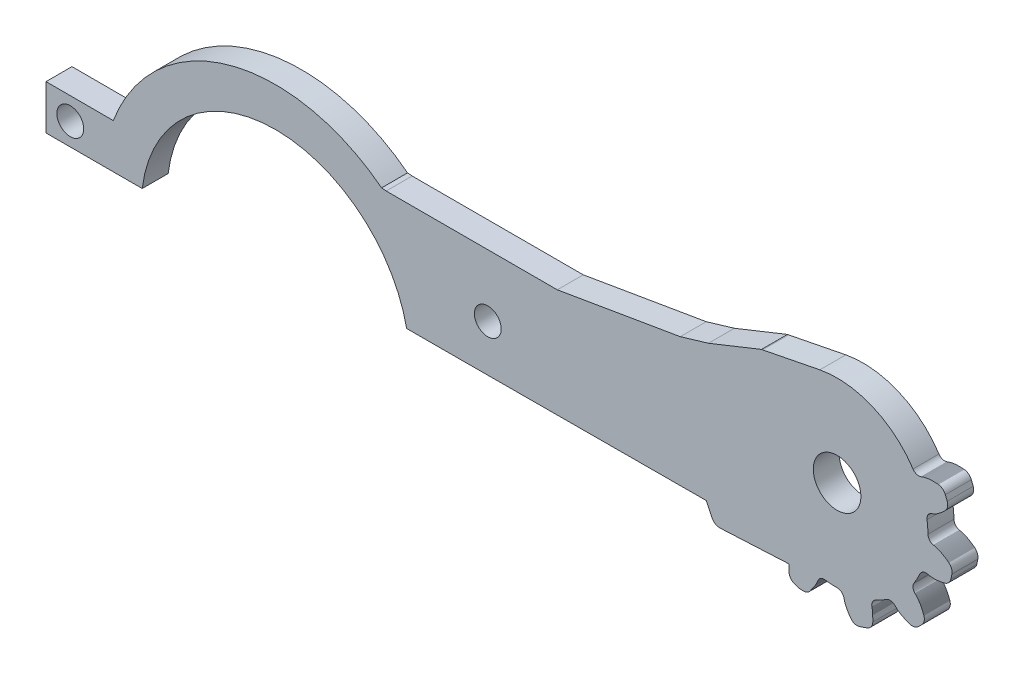
SolidWorks part; units mm, degrees
ref_plane "前视基准面" through (0, 0, 0) normal (0, 0, 1) x (1, 0, 0)
ref_plane "上视基准面" through (0, 0, 0) normal (0, 1, 0) x (1, 0, 0)
ref_plane "右视基准面" through (0, 0, 0) normal (1, 0, 0) x (0, 0, -1)
sketch "Model" plane through (0, 0, 0) normal (0, 0, 1) x (1, 0, 0)
  line L0 (3139.6381, 1742.7841) -> (3139.6125, 1742.8095)
  line L1 (3139.6635, 1742.7586) -> (3139.6381, 1742.7841)
  line L2 (3139.8365, 1742.5753) -> (3139.8124, 1742.602)
  line L3 (3153.0408, 1740.3213) -> (3153.0525, 1740.3554)
  line L4 (3153.0289, 1740.2873) -> (3153.0408, 1740.3213)
  line L5 (3153.0169, 1740.2533) -> (3153.0289, 1740.2873)
  line L6 (3153.0046, 1740.2194) -> (3153.0169, 1740.2533)
  line L7 (3152.9921, 1740.1856) -> (3153.0046, 1740.2194)
  line L8 (3152.9795, 1740.1519) -> (3152.9921, 1740.1856)
  line L9 (3152.87, 1739.8856) -> (3152.8846, 1739.9185)
  line L10 (3152.8242, 1739.788) -> (3152.8398, 1739.8203)
  line L11 (3154.7478, 1736.7119) -> (3154.7132, 1736.7018)
  line L12 (3154.7825, 1736.7216) -> (3154.7478, 1736.7119)
  line L13 (3154.8172, 1736.7308) -> (3154.7825, 1736.7216)
  line L14 (3154.8521, 1736.7395) -> (3154.8172, 1736.7308)
  line L15 (3154.8871, 1736.7479) -> (3154.8521, 1736.7395)
  line L16 (3154.9222, 1736.7557) -> (3154.8871, 1736.7479)
  line L17 (3154.9574, 1736.7631) -> (3154.9222, 1736.7557)
  line L18 (3154.9926, 1736.77) -> (3154.9574, 1736.7631)
  line L19 (3155.028, 1736.7765) -> (3154.9926, 1736.77)
  line L20 (3155.0634, 1736.7826) -> (3155.028, 1736.7765)
  line L21 (3155.1344, 1736.7936) -> (3155.0989, 1736.7883)
  line L22 (3155.17, 1736.7985) -> (3155.1344, 1736.7936)
  line L23 (3156.468, 1733.9968) -> (3156.497, 1734.0182)
  line L24 (3156.4389, 1733.9757) -> (3156.468, 1733.9968)
  line L25 (3156.4096, 1733.9547) -> (3156.4389, 1733.9757)
  line L26 (3156.3802, 1733.9339) -> (3156.4096, 1733.9547)
  line L27 (3156.3506, 1733.9134) -> (3156.3802, 1733.9339)
  line L28 (3156.3209, 1733.8931) -> (3156.3506, 1733.9134)
  line L29 (3156.291, 1733.8731) -> (3156.3209, 1733.8931)
  line L30 (3156.2609, 1733.8533) -> (3156.291, 1733.8731)
  line L31 (3156.2307, 1733.8339) -> (3156.2609, 1733.8533)
  line L32 (3156.2003, 1733.8148) -> (3156.2307, 1733.8339)
  line L33 (3156.1696, 1733.796) -> (3156.2003, 1733.8148)
  line L34 (3156.4614, 1730.0427) -> (3156.4285, 1730.0571)
  line L35 (3156.4942, 1730.028) -> (3156.4614, 1730.0427)
  line L36 (3156.5269, 1730.0129) -> (3156.4942, 1730.028)
  line L37 (3155.2801, 1726.9965) -> (3155.3155, 1726.99)
  line L38 (3155.2448, 1727.0034) -> (3155.2801, 1726.9965)
  line L39 (3155.1394, 1727.0265) -> (3155.1744, 1727.0185)
  line L40 (3155.1044, 1727.035) -> (3155.1394, 1727.0265)
  line L41 (3154.7261, 1727.0734) -> (3155.1044, 1727.035)
  line L42 (3139.9527, 1742.4382) -> (3139.9301, 1742.4661)
  line L43 (3139.9751, 1742.4101) -> (3139.9527, 1742.4382)
  line L44 (3152.9666, 1740.1183) -> (3152.9795, 1740.1519)
  line L45 (3152.9267, 1740.0179) -> (3152.9402, 1740.0512)
  line L46 (3152.8989, 1739.9515) -> (3152.9129, 1739.9846)
  line L47 (3152.8846, 1739.9185) -> (3152.8989, 1739.9515)
  line L48 (3155.3488, 1736.8185) -> (3155.313, 1736.8151)
  line L49 (3152.8551, 1739.8529) -> (3152.87, 1739.8856)
  line L50 (3152.8398, 1739.8203) -> (3152.8551, 1739.8529)
  line L51 (3152.8082, 1739.7558) -> (3152.8242, 1739.788)
  line L52 (3152.7919, 1739.7238) -> (3152.8082, 1739.7558)
  line L53 (3155.2095, 1727.0108) -> (3155.2448, 1727.0034)
  line L54 (3155.951, 1730.2151) -> (3155.916, 1730.2232)
  line L55 (3139.8603, 1742.5483) -> (3139.8365, 1742.5753)
  line L56 (3139.8838, 1742.5212) -> (3139.8603, 1742.5483)
  line L57 (3139.9071, 1742.4938) -> (3139.8838, 1742.5212)
  line L58 (3139.9301, 1742.4661) -> (3139.9071, 1742.4938)
  line L59 (3139.997, 1742.3817) -> (3139.9751, 1742.4101)
  line L60 (3152.9535, 1740.0847) -> (3152.9666, 1740.1183)
  line L61 (3152.9402, 1740.0512) -> (3152.9535, 1740.0847)
  line L62 (3140.0607, 1742.2947) -> (3140.0399, 1742.324)
  line L63 (3155.2057, 1736.8031) -> (3155.17, 1736.7985)
  line L64 (3152.9129, 1739.9846) -> (3152.9267, 1740.0179)
  line L65 (3156.497, 1734.0182) -> (3156.5259, 1734.0397)
  line L66 (3154.179, 1723.2587) -> (3154.162, 1723.2905)
  line L67 (3154.1959, 1723.2269) -> (3154.179, 1723.2587)
  line L68 (3154.2125, 1723.1949) -> (3154.1959, 1723.2269)
  line L69 (3154.2289, 1723.1628) -> (3154.2125, 1723.1949)
  line L70 (3154.2452, 1723.1307) -> (3154.2289, 1723.1628)
  line L71 (3154.2612, 1723.0984) -> (3154.2452, 1723.1307)
  line L72 (3154.277, 1723.066) -> (3154.2612, 1723.0984)
  line L73 (3154.2927, 1723.0336) -> (3154.277, 1723.066)
  line L74 (3154.3081, 1723.001) -> (3154.2927, 1723.0336)
  line L75 (3154.3338, 1722.9732) -> (3154.3081, 1723.001)
  line L76 (3152.3422, 1721.044) -> (3152.3796, 1721.0389)
  line L77 (3152.3097, 1721.0596) -> (3152.3422, 1721.044)
  line L78 (3152.2773, 1721.0754) -> (3152.3097, 1721.0596)
  line L79 (3155.0989, 1736.7883) -> (3155.0634, 1736.7826)
  line L80 (3140.0399, 1742.324) -> (3140.0186, 1742.353)
  line L81 (3156.0903, 1730.1784) -> (3156.0556, 1730.1882)
  line L82 (3156.1248, 1730.1682) -> (3156.0903, 1730.1784)
  line L83 (3152.2451, 1721.0914) -> (3152.2773, 1721.0754)
  line L84 (3152.2129, 1721.1075) -> (3152.2451, 1721.0914)
  line L85 (3156.4285, 1730.0571) -> (3156.3954, 1730.0711)
  line L86 (3146.7836, 1742.877) -> (3146.781, 1742.9128)
  line L87 (3146.7858, 1742.8411) -> (3146.7836, 1742.877)
  line L88 (3146.7875, 1742.8052) -> (3146.7858, 1742.8411)
  line L89 (3146.7888, 1742.7692) -> (3146.7875, 1742.8052)
  line L90 (3146.7896, 1742.7333) -> (3146.7888, 1742.7692)
  line L91 (3146.7899, 1742.6973) -> (3146.7896, 1742.7333)
  line L92 (3146.7898, 1742.6613) -> (3146.7899, 1742.6973)
  line L93 (3146.7893, 1742.6253) -> (3146.7898, 1742.6613)
  line L94 (3146.7883, 1742.5893) -> (3146.7893, 1742.6253)
  line L95 (3146.7869, 1742.5533) -> (3146.7883, 1742.5893)
  line L96 (3146.7851, 1742.5174) -> (3146.7869, 1742.5533)
  line L97 (3146.7828, 1742.4815) -> (3146.7851, 1742.5174)
  line L98 (3146.7802, 1742.4456) -> (3146.7828, 1742.4815)
  line L99 (3146.7772, 1742.4097) -> (3146.7802, 1742.4456)
  line L100 (3146.7738, 1742.374) -> (3146.7772, 1742.4097)
  line L101 (3146.7513, 1741.9979) -> (3146.7738, 1742.374)
  line L102 (3149.8509, 1741.2183) -> (3149.6326, 1740.9116)
  line L103 (3140.0186, 1742.353) -> (3139.997, 1742.3817)
  line L104 (3149.8719, 1741.2475) -> (3149.8509, 1741.2183)
  line L105 (3149.8932, 1741.2765) -> (3149.8719, 1741.2475)
  line L106 (3149.9149, 1741.3052) -> (3149.8932, 1741.2765)
  line L107 (3155.2414, 1736.8074) -> (3155.2057, 1736.8031)
  line L108 (3155.2772, 1736.8114) -> (3155.2414, 1736.8074)
  line L109 (3155.313, 1736.8151) -> (3155.2772, 1736.8114)
  line L110 (3156.4629, 1726.9866) -> (3156.4986, 1726.9911)
  line L111 (3156.4271, 1726.9824) -> (3156.4629, 1726.9866)
  line L112 (3155.986, 1730.2065) -> (3155.951, 1730.2151)
  line L113 (3156.0209, 1730.1976) -> (3155.986, 1730.2065)
  line L114 (3156.0556, 1730.1882) -> (3156.0209, 1730.1976)
  line L115 (3156.1592, 1730.1576) -> (3156.1248, 1730.1682)
  line L116 (3156.7523, 1734.2181) -> (3156.7799, 1734.2412)
  line L117 (3156.7245, 1734.1952) -> (3156.7523, 1734.2181)
  line L118 (3156.6965, 1734.1725) -> (3156.7245, 1734.1952)
  line L119 (3156.6684, 1734.1499) -> (3156.6965, 1734.1725)
  line L120 (3156.6402, 1734.1275) -> (3156.6684, 1734.1499)
  line L121 (3156.6118, 1734.1053) -> (3156.6402, 1734.1275)
  line L122 (3156.5833, 1734.0833) -> (3156.6118, 1734.1053)
  line L123 (3156.5547, 1734.0614) -> (3156.5833, 1734.0833)
  line L124 (3156.5259, 1734.0397) -> (3156.5547, 1734.0614)
  line L125 (3153.0639, 1740.3896) -> (3153.0751, 1740.4238)
  line L126 (3153.0525, 1740.3554) -> (3153.0639, 1740.3896)
  line L127 (3155.2459, 1733.3476) -> (3155.5833, 1733.5244)
  line L128 (3156.1934, 1730.1466) -> (3156.1592, 1730.1576)
  line L129 (3156.2275, 1730.1351) -> (3156.1934, 1730.1466)
  line L130 (3156.2615, 1730.1232) -> (3156.2275, 1730.1351)
  line L131 (3156.2952, 1730.1108) -> (3156.2615, 1730.1232)
  line L132 (3156.3288, 1730.098) -> (3156.2952, 1730.1108)
  line L133 (3156.3622, 1730.0848) -> (3156.3288, 1730.098)
  line L134 (3156.3954, 1730.0711) -> (3156.3622, 1730.0848)
  line L135 (3143.5454, 1743.0444) -> (3143.5389, 1743.0091)
  line L136 (3143.5524, 1743.0797) -> (3143.5454, 1743.0444)
  line L137 (3143.5598, 1743.1149) -> (3143.5524, 1743.0797)
  line L138 (3143.5677, 1743.15) -> (3143.5598, 1743.1149)
  line L139 (3143.5761, 1743.1849) -> (3143.5677, 1743.15)
  line L140 (3143.5848, 1743.2197) -> (3143.5761, 1743.1849)
  line L141 (3143.594, 1743.2545) -> (3143.5848, 1743.2197)
  line L142 (3143.6036, 1743.2891) -> (3143.594, 1743.2545)
  line L143 (3143.6135, 1743.3237) -> (3143.6036, 1743.2891)
  line L144 (3143.6345, 1743.3925) -> (3143.6238, 1743.3581)
  line L145 (3143.6454, 1743.4267) -> (3143.6345, 1743.3925)
  line L146 (3143.6567, 1743.4609) -> (3143.6454, 1743.4267)
  line L147 (3143.6682, 1743.495) -> (3143.6567, 1743.4609)
  line L148 (3143.68, 1743.5291) -> (3143.6682, 1743.495)
  line L149 (3143.686, 1743.546) -> (3143.68, 1743.5291)
  line L150 (3156.1388, 1733.7775) -> (3156.1696, 1733.796)
  line L151 (3156.1077, 1733.7594) -> (3156.1388, 1733.7775)
  line L152 (3155.5833, 1733.5244) -> (3155.6173, 1733.5362)
  line L153 (3155.8104, 1730.2453) -> (3155.4407, 1730.3164)
  line L154 (3155.8457, 1730.2383) -> (3155.8104, 1730.2453)
  line L155 (3155.8809, 1730.231) -> (3155.8457, 1730.2383)
  line L156 (3155.916, 1730.2232) -> (3155.8809, 1730.231)
  line L157 (3146.7256, 1743.3043) -> (3146.7187, 1743.3396)
  line L158 (3146.7323, 1743.2689) -> (3146.7256, 1743.3043)
  line L159 (3146.7387, 1743.2335) -> (3146.7323, 1743.2689)
  line L160 (3146.7448, 1743.198) -> (3146.7387, 1743.2335)
  line L161 (3146.7506, 1743.1625) -> (3146.7448, 1743.198)
  line L162 (3146.7561, 1743.127) -> (3146.7506, 1743.1625)
  line L163 (3146.7612, 1743.0914) -> (3146.7561, 1743.127)
  line L164 (3146.7659, 1743.0557) -> (3146.7612, 1743.0914)
  line L165 (3146.7703, 1743.0201) -> (3146.7659, 1743.0557)
  line L166 (3146.7743, 1742.9844) -> (3146.7703, 1743.0201)
  line L167 (3146.7779, 1742.9486) -> (3146.7743, 1742.9844)
  line L168 (3146.781, 1742.9128) -> (3146.7779, 1742.9486)
  line L169 (3153.0969, 1740.4925) -> (3153.0997, 1740.5293)
  line L170 (3156.0765, 1733.7417) -> (3156.1077, 1733.7594)
  line L171 (3155.7852, 1733.6007) -> (3155.8184, 1733.6147)
  line L172 (3155.7519, 1733.587) -> (3155.7852, 1733.6007)
  line L173 (3155.7185, 1733.5737) -> (3155.7519, 1733.587)
  line L174 (3155.6849, 1733.5608) -> (3155.7185, 1733.5737)
  line L175 (3155.6512, 1733.5483) -> (3155.6849, 1733.5608)
  line L176 (3155.6173, 1733.5362) -> (3155.6512, 1733.5483)
  line L177 (3151.8657, 1721.2984) -> (3151.8967, 1721.28)
  line L178 (3152.7752, 1739.692) -> (3152.7919, 1739.7238)
  line L179 (3152.7225, 1739.5979) -> (3152.7405, 1739.629)
  line L180 (3139.5087, 1742.9095) -> (3139.4824, 1742.9341)
  line L181 (3139.5349, 1742.8847) -> (3139.5087, 1742.9095)
  line L182 (3139.5609, 1742.8598) -> (3139.5349, 1742.8847)
  line L183 (3139.5868, 1742.8347) -> (3139.5609, 1742.8598)
  line L184 (3139.6125, 1742.8095) -> (3139.5868, 1742.8347)
  line L185 (3154.5424, 1736.6452) -> (3154.5087, 1736.6328)
  line L186 (3139.6888, 1742.7329) -> (3139.6635, 1742.7586)
  line L187 (3139.7139, 1742.707) -> (3139.6888, 1742.7329)
  line L188 (3139.7388, 1742.6811) -> (3139.7139, 1742.707)
  line L189 (3139.7635, 1742.6549) -> (3139.7388, 1742.6811)
  line L190 (3139.7881, 1742.6285) -> (3139.7635, 1742.6549)
  line L191 (3139.8124, 1742.602) -> (3139.7881, 1742.6285)
  line L192 (3140.0812, 1742.2651) -> (3140.0607, 1742.2947)
  line L193 (3140.1013, 1742.2353) -> (3140.0812, 1742.2651)
  line L194 (3140.1211, 1742.2052) -> (3140.1013, 1742.2353)
  line L195 (3140.1404, 1742.1748) -> (3140.1211, 1742.2052)
  line L196 (3140.1594, 1742.1443) -> (3140.1404, 1742.1748)
  line L197 (3140.1781, 1742.1135) -> (3140.1594, 1742.1443)
  line L198 (3140.1963, 1742.0824) -> (3140.1781, 1742.1135)
  line L199 (3140.2143, 1742.0512) -> (3140.1963, 1742.0824)
  line L200 (3140.2318, 1742.0198) -> (3140.2143, 1742.0512)
  line L201 (3140.249, 1741.9882) -> (3140.2318, 1742.0198)
  line L202 (3140.2658, 1741.9564) -> (3140.249, 1741.9882)
  line L203 (3140.2823, 1741.9245) -> (3140.2658, 1741.9564)
  line L204 (3140.4359, 1741.5802) -> (3140.2823, 1741.9245)
  line L205 (3143.4957, 1742.6159) -> (3143.4779, 1742.2399)
  line L206 (3143.4976, 1742.6518) -> (3143.4957, 1742.6159)
  line L207 (3143.4999, 1742.6877) -> (3143.4976, 1742.6518)
  line L208 (3143.5026, 1742.7235) -> (3143.4999, 1742.6877)
  line L209 (3143.5056, 1742.7594) -> (3143.5026, 1742.7235)
  line L210 (3143.5091, 1742.7952) -> (3143.5056, 1742.7594)
  line L211 (3143.513, 1742.831) -> (3143.5091, 1742.7952)
  line L212 (3143.5173, 1742.8668) -> (3143.513, 1742.831)
  line L213 (3143.5221, 1742.9024) -> (3143.5173, 1742.8668)
  line L214 (3143.5272, 1742.9381) -> (3143.5221, 1742.9024)
  line L215 (3143.5329, 1742.9736) -> (3143.5272, 1742.9381)
  line L216 (3143.5389, 1743.0091) -> (3143.5329, 1742.9736)
  line L217 (3154.0741, 1723.4476) -> (3154.0559, 1723.4787)
  line L218 (3154.0921, 1723.4164) -> (3154.0741, 1723.4476)
  line L219 (3154.1099, 1723.3851) -> (3154.0921, 1723.4164)
  line L220 (3154.1274, 1723.3537) -> (3154.1099, 1723.3851)
  line L221 (3154.1448, 1723.3221) -> (3154.1274, 1723.3537)
  line L222 (3154.162, 1723.2905) -> (3154.1448, 1723.3221)
  line L223 (3150.8201, 1742.1198) -> (3150.7904, 1742.0996)
  line L224 (3150.85, 1742.1399) -> (3150.8201, 1742.1198)
  line L225 (3150.8801, 1742.1598) -> (3150.85, 1742.1399)
  line L226 (3150.9061, 1742.1859) -> (3150.8801, 1742.1598)
  line L227 (3153.0861, 1740.4581) -> (3153.0969, 1740.4925)
  line L228 (3153.0751, 1740.4238) -> (3153.0861, 1740.4581)
  line L229 (3156.045, 1733.7244) -> (3156.0765, 1733.7417)
  line L230 (3156.0133, 1733.7075) -> (3156.045, 1733.7244)
  line L231 (3155.9491, 1733.675) -> (3155.9813, 1733.691)
  line L232 (3155.9167, 1733.6593) -> (3155.9491, 1733.675)
  line L233 (3155.8841, 1733.644) -> (3155.9167, 1733.6593)
  line L234 (3155.8513, 1733.6292) -> (3155.8841, 1733.644)
  line L235 (3155.8184, 1733.6147) -> (3155.8513, 1733.6292)
  line L236 (3152.0851, 1721.1742) -> (3152.1169, 1721.1573)
  line L237 (3152.0534, 1721.1914) -> (3152.0851, 1721.1742)
  line L238 (3152.0218, 1721.2087) -> (3152.0534, 1721.1914)
  line L239 (3151.9904, 1721.2263) -> (3152.0218, 1721.2087)
  line L240 (3151.959, 1721.244) -> (3151.9904, 1721.2263)
  line L241 (3151.9278, 1721.2619) -> (3151.959, 1721.244)
  line L242 (3151.8967, 1721.28) -> (3151.9278, 1721.2619)
  line L243 (3150.0998, 1741.5257) -> (3150.0755, 1741.4992)
  line L244 (3151.7135, 1721.3942) -> (3151.7436, 1721.3744)
  line L245 (3151.6837, 1721.4142) -> (3151.7135, 1721.3942)
  line L246 (3151.6247, 1721.4553) -> (3151.6541, 1721.4346)
  line L247 (3151.5956, 1721.4764) -> (3151.6247, 1721.4553)
  line L248 (3151.5668, 1721.4979) -> (3151.5956, 1721.4764)
  line L249 (3151.5383, 1721.5197) -> (3151.5668, 1721.4979)
  line L250 (3151.51, 1721.5419) -> (3151.5383, 1721.5197)
  line L251 (3151.482, 1721.5645) -> (3151.51, 1721.5419)
  line L252 (3151.4543, 1721.5875) -> (3151.482, 1721.5645)
  line L253 (3151.4269, 1721.6108) -> (3151.4543, 1721.5875)
  line L254 (3151.3998, 1721.6345) -> (3151.4269, 1721.6108)
  line L255 (3151.3729, 1721.6584) -> (3151.3998, 1721.6345)
  line L256 (3151.3464, 1721.6827) -> (3151.3729, 1721.6584)
  line L257 (3151.3201, 1721.7074) -> (3151.3464, 1721.6827)
  line L258 (3151.2941, 1721.7323) -> (3151.3201, 1721.7074)
  line L259 (3151.2684, 1721.7575) -> (3151.2941, 1721.7323)
  line L260 (3151.243, 1721.783) -> (3151.2684, 1721.7575)
  line L261 (3151.2179, 1721.8087) -> (3151.243, 1721.783)
  line L262 (3151.1931, 1721.8347) -> (3151.2179, 1721.8087)
  line L263 (3150.9347, 1722.1084) -> (3151.1931, 1721.8347)
  line L264 (3155.1744, 1727.0185) -> (3155.2095, 1727.0108)
  line L265 (3156.8465, 1729.8473) -> (3156.815, 1729.8648)
  line L266 (3156.8779, 1729.8296) -> (3156.8465, 1729.8473)
  line L267 (3149.9368, 1741.3337) -> (3149.9149, 1741.3052)
  line L268 (3149.9591, 1741.3619) -> (3149.9368, 1741.3337)
  line L269 (3149.9818, 1741.3899) -> (3149.9591, 1741.3619)
  line L270 (3150.0047, 1741.4177) -> (3149.9818, 1741.3899)
  line L271 (3150.028, 1741.4451) -> (3150.0047, 1741.4177)
  line L272 (3150.0516, 1741.4723) -> (3150.028, 1741.4451)
  line L273 (3150.0755, 1741.4992) -> (3150.0516, 1741.4723)
  line L274 (3155.4565, 1736.8273) -> (3155.4206, 1736.8246)
  line L275 (3150.1244, 1741.552) -> (3150.0998, 1741.5257)
  line L276 (3150.1493, 1741.5779) -> (3150.1244, 1741.552)
  line L277 (3150.1746, 1741.6034) -> (3150.1493, 1741.5779)
  line L278 (3150.2002, 1741.6287) -> (3150.1746, 1741.6034)
  line L279 (3150.2261, 1741.6536) -> (3150.2002, 1741.6287)
  line L280 (3150.2523, 1741.6781) -> (3150.2261, 1741.6536)
  line L281 (3150.2788, 1741.7024) -> (3150.2523, 1741.6781)
  line L282 (3150.3056, 1741.7264) -> (3150.2788, 1741.7024)
  line L283 (3150.3327, 1741.7501) -> (3150.3056, 1741.7264)
  line L284 (3150.36, 1741.7735) -> (3150.3327, 1741.7501)
  line L285 (3150.3875, 1741.7966) -> (3150.36, 1741.7735)
  line L286 (3150.4152, 1741.8195) -> (3150.3875, 1741.7966)
  line L287 (3150.4432, 1741.8422) -> (3150.4152, 1741.8195)
  line L288 (3150.4713, 1741.8647) -> (3150.4432, 1741.8422)
  line L289 (3150.4996, 1741.8869) -> (3150.4713, 1741.8647)
  line L290 (3150.5281, 1741.909) -> (3150.4996, 1741.8869)
  line L291 (3150.5567, 1741.9308) -> (3150.5281, 1741.909)
  line L292 (3150.5854, 1741.9525) -> (3150.5567, 1741.9308)
  line L293 (3150.6143, 1741.9741) -> (3150.5854, 1741.9525)
  line L294 (3150.6433, 1741.9954) -> (3150.6143, 1741.9741)
  line L295 (3150.6725, 1742.0166) -> (3150.6433, 1741.9954)
  line L296 (3150.7018, 1742.0376) -> (3150.6725, 1742.0166)
  line L297 (3150.7312, 1742.0584) -> (3150.7018, 1742.0376)
  line L298 (3150.7607, 1742.0791) -> (3150.7312, 1742.0584)
  line L299 (3150.7904, 1742.0996) -> (3150.7607, 1742.0791)
  line L300 (3155.3865, 1726.9783) -> (3155.4221, 1726.973)
  line L301 (3155.351, 1726.9839) -> (3155.3865, 1726.9783)
  line L302 (3155.3155, 1726.99) -> (3155.351, 1726.9839)
  line L303 (3154.6103, 1736.6691) -> (3154.5763, 1736.6573)
  line L304 (3154.6445, 1736.6804) -> (3154.6103, 1736.6691)
  line L305 (3154.6788, 1736.6913) -> (3154.6445, 1736.6804)
  line L306 (3154.7132, 1736.7018) -> (3154.6788, 1736.6913)
  line L307 (3156.7517, 1729.8993) -> (3156.7199, 1729.9162)
  line L308 (3156.7834, 1729.8821) -> (3156.7517, 1729.8993)
  line L309 (3156.815, 1729.8648) -> (3156.7834, 1729.8821)
  line L310 (3152.6853, 1739.5363) -> (3152.7041, 1739.5669)
  line L311 (3152.6662, 1739.5058) -> (3152.6853, 1739.5363)
  line L312 (3156.9091, 1729.8117) -> (3156.8779, 1729.8296)
  line L313 (3156.9403, 1729.7936) -> (3156.9091, 1729.8117)
  line L314 (3156.9713, 1729.7753) -> (3156.9403, 1729.7936)
  line L315 (3155.9813, 1733.691) -> (3156.0133, 1733.7075)
  line L316 (3157.0331, 1729.7381) -> (3157.0023, 1729.7568)
  line L317 (3157.0638, 1729.7193) -> (3157.0331, 1729.7381)
  line L318 (3152.1808, 1721.1239) -> (3152.2129, 1721.1075)
  line L319 (3152.1488, 1721.1405) -> (3152.1808, 1721.1239)
  line L320 (3152.1169, 1721.1573) -> (3152.1488, 1721.1405)
  line L321 (3153.5226, 1724.1537) -> (3153.2501, 1724.4134)
  line L322 (3153.5485, 1724.1288) -> (3153.5226, 1724.1537)
  line L323 (3155.3847, 1736.8216) -> (3155.3488, 1736.8185)
  line L324 (3155.4206, 1736.8246) -> (3155.3847, 1736.8216)
  line L325 (3156.3913, 1726.9784) -> (3156.4271, 1726.9824)
  line L326 (3155.4925, 1736.8298) -> (3155.4565, 1736.8273)
  line L327 (3151.8349, 1721.317) -> (3151.8657, 1721.2984)
  line L328 (3151.8043, 1721.3359) -> (3151.8349, 1721.317)
  line L329 (3152.758, 1739.6604) -> (3152.7752, 1739.692)
  line L330 (3152.7405, 1739.629) -> (3152.758, 1739.6604)
  line L331 (3155.7084, 1736.8402) -> (3155.6724, 1736.839)
  line L332 (3152.7041, 1739.5669) -> (3152.7225, 1739.5979)
  line L333 (3155.7444, 1736.8411) -> (3155.7084, 1736.8402)
  line L334 (3155.7804, 1736.8419) -> (3155.7444, 1736.8411)
  line L335 (3152.6466, 1739.4756) -> (3152.6662, 1739.5058)
  line L336 (3152.6267, 1739.4456) -> (3152.6466, 1739.4756)
  line L337 (3152.6064, 1739.4159) -> (3152.6267, 1739.4456)
  line L338 (3152.5858, 1739.3864) -> (3152.6064, 1739.4159)
  line L339 (3152.5648, 1739.3571) -> (3152.5858, 1739.3864)
  line L340 (3152.5435, 1739.3281) -> (3152.5648, 1739.3571)
  line L341 (3152.5219, 1739.2993) -> (3152.5435, 1739.3281)
  line L342 (3152.5, 1739.2708) -> (3152.5219, 1739.2993)
  line L343 (3152.4778, 1739.2425) -> (3152.5, 1739.2708)
  line L344 (3152.2785, 1738.9201) -> (3152.4778, 1739.2425)
  line L345 (3154.4416, 1736.6067) -> (3154.0922, 1736.4667)
  line L346 (3154.4751, 1736.6199) -> (3154.4416, 1736.6067)
  line L347 (3154.5087, 1736.6328) -> (3154.4751, 1736.6199)
  line L348 (3156.5593, 1729.9974) -> (3156.5269, 1730.0129)
  line L349 (3154.5763, 1736.6573) -> (3154.5424, 1736.6452)
  line L350 (3156.5917, 1729.9817) -> (3156.5593, 1729.9974)
  line L351 (3156.6239, 1729.9657) -> (3156.5917, 1729.9817)
  line L352 (3156.6561, 1729.9495) -> (3156.6239, 1729.9657)
  line L353 (3156.6881, 1729.933) -> (3156.6561, 1729.9495)
  line L354 (3156.7199, 1729.9162) -> (3156.6881, 1729.933)
  line L355 (3156.14, 1726.9564) -> (3156.176, 1726.9589)
  line L356 (3153.7455, 1723.9189) -> (3153.7219, 1723.9461)
  line L357 (3156.1041, 1726.9542) -> (3156.14, 1726.9564)
  line L358 (3155.8165, 1736.8424) -> (3155.7804, 1736.8419)
  line L359 (3155.8524, 1736.8561) -> (3155.8165, 1736.8424)
  line L360 (3153.9206, 1723.6909) -> (3153.9, 1723.7203)
  line L361 (3157.0023, 1729.7568) -> (3156.9713, 1729.7753)
  line L362 (3156.7799, 1734.2412) -> (3156.7986, 1734.2749)
  line L363 (3157.0944, 1729.7002) -> (3157.0638, 1729.7193)
  line L364 (3157.1328, 1729.6935) -> (3157.0944, 1729.7002)
  line L365 (3156.4986, 1726.9911) -> (3156.5323, 1727.0105)
  line L366 (3153.5741, 1724.1035) -> (3153.5485, 1724.1288)
  line L367 (3156.3554, 1726.9746) -> (3156.3913, 1726.9784)
  line L368 (3155.5284, 1736.8321) -> (3155.4925, 1736.8298)
  line L369 (3155.5644, 1736.8341) -> (3155.5284, 1736.8321)
  line L370 (3155.6004, 1736.836) -> (3155.5644, 1736.8341)
  line L371 (3155.6364, 1736.8376) -> (3155.6004, 1736.836)
  line L372 (3155.6724, 1736.839) -> (3155.6364, 1736.8376)
  line L373 (3151.7436, 1721.3744) -> (3151.7738, 1721.355)
  line L374 (3156.176, 1726.9589) -> (3156.2119, 1726.9616)
  line L375 (3151.6541, 1721.4346) -> (3151.6837, 1721.4142)
  line L376 (3156.0321, 1726.9503) -> (3156.0681, 1726.9521)
  line L377 (3153.9409, 1723.6612) -> (3153.9206, 1723.6909)
  line L378 (3154.0187, 1723.5403) -> (3153.9997, 1723.5708)
  line L379 (3154.0374, 1723.5096) -> (3154.0187, 1723.5403)
  line L380 (3154.0559, 1723.4787) -> (3154.0374, 1723.5096)
  line L381 (3155.6009, 1726.9537) -> (3155.6368, 1726.9512)
  line L382 (3155.5651, 1726.9566) -> (3155.6009, 1726.9537)
  line L383 (3155.5293, 1726.96) -> (3155.5651, 1726.9566)
  line L384 (3155.4935, 1726.9639) -> (3155.5293, 1726.96)
  line L385 (3155.4578, 1726.9683) -> (3155.4935, 1726.9639)
  line L386 (3155.4221, 1726.973) -> (3155.4578, 1726.9683)
  line L387 (3153.5995, 1724.078) -> (3153.5741, 1724.1035)
  line L388 (3156.3196, 1726.971) -> (3156.3554, 1726.9746)
  line L389 (3156.2837, 1726.9677) -> (3156.3196, 1726.971)
  line L390 (3156.2478, 1726.9645) -> (3156.2837, 1726.9677)
  line L391 (3151.7738, 1721.355) -> (3151.8043, 1721.3359)
  line L392 (3156.2119, 1726.9616) -> (3156.2478, 1726.9645)
  line L393 (3153.6981, 1723.9731) -> (3153.6739, 1723.9997)
  line L394 (3153.7219, 1723.9461) -> (3153.6981, 1723.9731)
  line L395 (3153.7686, 1723.8914) -> (3153.7455, 1723.9189)
  line L396 (3156.0681, 1726.9521) -> (3156.1041, 1726.9542)
  line L397 (3153.814, 1723.8355) -> (3153.7915, 1723.8636)
  line L398 (3155.9962, 1726.9487) -> (3156.0321, 1726.9503)
  line L399 (3155.9242, 1726.9465) -> (3155.9602, 1726.9475)
  line L400 (3155.8883, 1726.9458) -> (3155.9242, 1726.9465)
  line L401 (3138.7876, 1743.2782) -> (3132.2952, 1743.1634)
  line L402 (3139.3756, 1743.0308) -> (3138.7876, 1743.2782)
  line L403 (3139.4025, 1743.0069) -> (3139.3756, 1743.0308)
  line L404 (3139.4293, 1742.9828) -> (3139.4025, 1743.0069)
  line L405 (3153.8791, 1723.7495) -> (3153.8578, 1723.7785)
  line L406 (3153.6246, 1724.0522) -> (3153.5995, 1724.078)
  line L407 (3153.6494, 1724.0261) -> (3153.6246, 1724.0522)
  line L408 (3153.6739, 1723.9997) -> (3153.6494, 1724.0261)
  line L409 (3155.7085, 1726.9476) -> (3155.7445, 1726.9465)
  line L410 (3153.7915, 1723.8636) -> (3153.7686, 1723.8914)
  line L411 (3155.9602, 1726.9475) -> (3155.9962, 1726.9487)
  line L412 (3153.8578, 1723.7785) -> (3153.8361, 1723.8071)
  line L413 (3155.8523, 1726.9454) -> (3155.8883, 1726.9458)
  line L414 (3155.8163, 1726.9454) -> (3155.8523, 1726.9454)
  line L415 (3155.7804, 1726.9458) -> (3155.8163, 1726.9454)
  line L416 (3155.7445, 1726.9465) -> (3155.7804, 1726.9458)
  line L417 (3153.9804, 1723.6012) -> (3153.9608, 1723.6313)
  line L418 (3139.4559, 1742.9585) -> (3139.4293, 1742.9828)
  line L419 (3139.4824, 1742.9341) -> (3139.4559, 1742.9585)
  line L420 (3153.8361, 1723.8071) -> (3153.814, 1723.8355)
  line L421 (3155.6726, 1726.9492) -> (3155.7085, 1726.9476)
  line L422 (3153.9, 1723.7203) -> (3153.8791, 1723.7495)
  line L423 (3153.9608, 1723.6313) -> (3153.9409, 1723.6612)
  line L424 (3155.6368, 1726.9512) -> (3155.6726, 1726.9492)
  line L425 (3153.9997, 1723.5708) -> (3153.9804, 1723.6012)
  line L426 (3131.4116, 1742.5968) -> (3131.1697, 1740.2313)
  line L427 (3159.0065, 1766.84) -> (3159.0349, 1766.8694)
  line L428 (3158.978, 1766.8108) -> (3159.0065, 1766.84)
  line L429 (3158.9492, 1766.7818) -> (3158.978, 1766.8108)
  line L430 (3158.9203, 1766.7529) -> (3158.9492, 1766.7818)
  line L431 (3158.8912, 1766.7242) -> (3158.9203, 1766.7529)
  line L432 (3158.8619, 1766.6957) -> (3158.8912, 1766.7242)
  line L433 (3158.8325, 1766.6674) -> (3158.8619, 1766.6957)
  line L434 (3158.8028, 1766.6393) -> (3158.8325, 1766.6674)
  line L435 (3158.773, 1766.6114) -> (3158.8028, 1766.6393)
  line L436 (3158.743, 1766.5837) -> (3158.773, 1766.6114)
  line L437 (3158.7128, 1766.5561) -> (3158.743, 1766.5837)
  line L438 (3158.6824, 1766.5288) -> (3158.7128, 1766.5561)
  line L439 (3158.6519, 1766.5017) -> (3158.6824, 1766.5288)
  line L440 (3158.6211, 1766.4747) -> (3158.6519, 1766.5017)
  line L441 (3158.5902, 1766.448) -> (3158.6211, 1766.4747)
  line L442 (3158.5591, 1766.4215) -> (3158.5902, 1766.448)
  line L443 (3158.5278, 1766.3952) -> (3158.5591, 1766.4215)
  line L444 (3158.4963, 1766.369) -> (3158.5278, 1766.3952)
  line L445 (3158.4647, 1766.3431) -> (3158.4963, 1766.369)
  line L446 (3158.4328, 1766.3175) -> (3158.4647, 1766.3431)
  line L447 (3158.4007, 1766.2921) -> (3158.4328, 1766.3175)
  line L448 (3158.3685, 1766.2669) -> (3158.4007, 1766.2921)
  line L449 (3158.336, 1766.242) -> (3158.3685, 1766.2669)
  line L450 (3158.3033, 1766.2174) -> (3158.336, 1766.242)
  line L451 (3158.2704, 1766.1932) -> (3158.3033, 1766.2174)
  line L452 (3158.2372, 1766.1693) -> (3158.2704, 1766.1932)
  line L453 (3158.2038, 1766.1457) -> (3158.2372, 1766.1693)
  line L454 (3158.1701, 1766.1225) -> (3158.2038, 1766.1457)
  line L455 (3158.1362, 1766.0997) -> (3158.1701, 1766.1225)
  line L456 (3158.102, 1766.0773) -> (3158.1362, 1766.0997)
  line L457 (3158.0676, 1766.0553) -> (3158.102, 1766.0773)
  line L458 (3158.0329, 1766.0338) -> (3158.0676, 1766.0553)
  line L459 (3157.9979, 1766.0127) -> (3158.0329, 1766.0338)
  line L460 (3157.9626, 1765.9921) -> (3157.9979, 1766.0127)
  line L461 (3157.927, 1765.972) -> (3157.9626, 1765.9921)
  line L462 (3157.8911, 1765.9523) -> (3157.927, 1765.972)
  line L463 (3157.8549, 1765.9332) -> (3157.8911, 1765.9523)
  line L464 (3157.8185, 1765.9145) -> (3157.8549, 1765.9332)
  line L465 (3157.7819, 1765.8963) -> (3157.8185, 1765.9145)
  line L466 (3157.745, 1765.8786) -> (3157.7819, 1765.8963)
  line L467 (3157.7079, 1765.8613) -> (3157.745, 1765.8786)
  line L468 (3157.6706, 1765.8445) -> (3157.7079, 1765.8613)
  line L469 (3157.6331, 1765.8281) -> (3157.6706, 1765.8445)
  line L470 (3157.5954, 1765.8122) -> (3157.6331, 1765.8281)
  line L471 (3157.5575, 1765.7968) -> (3157.5954, 1765.8122)
  line L472 (3157.5195, 1765.7818) -> (3157.5575, 1765.7968)
  line L473 (3157.4813, 1765.7673) -> (3157.5195, 1765.7818)
  line L474 (3157.4429, 1765.7532) -> (3157.4813, 1765.7673)
  line L475 (3157.7178, 1762.7102) -> (3157.6777, 1762.7182)
  line L476 (3157.7578, 1762.7017) -> (3157.7178, 1762.7102)
  line L477 (3157.7977, 1762.6928) -> (3157.7578, 1762.7017)
  line L478 (3157.8375, 1762.6833) -> (3157.7977, 1762.6928)
  line L479 (3157.8772, 1762.6734) -> (3157.8375, 1762.6833)
  line L480 (3157.9168, 1762.663) -> (3157.8772, 1762.6734)
  line L481 (3157.9562, 1762.6522) -> (3157.9168, 1762.663)
  line L482 (3157.9955, 1762.6408) -> (3157.9562, 1762.6522)
  line L483 (3158.0347, 1762.629) -> (3157.9955, 1762.6408)
  line L484 (3158.0737, 1762.6166) -> (3158.0347, 1762.629)
  line L485 (3158.1125, 1762.6038) -> (3158.0737, 1762.6166)
  line L486 (3158.1512, 1762.5904) -> (3158.1125, 1762.6038)
  line L487 (3158.1897, 1762.5765) -> (3158.1512, 1762.5904)
  line L488 (3158.2279, 1762.5621) -> (3158.1897, 1762.5765)
  line L489 (3158.266, 1762.5472) -> (3158.2279, 1762.5621)
  line L490 (3158.3038, 1762.5317) -> (3158.266, 1762.5472)
  line L491 (3158.3414, 1762.5158) -> (3158.3038, 1762.5317)
  line L492 (3158.3789, 1762.4994) -> (3158.3414, 1762.5158)
  line L493 (3158.4161, 1762.4825) -> (3158.3789, 1762.4994)
  line L494 (3158.4531, 1762.4652) -> (3158.4161, 1762.4825)
  line L495 (3158.4899, 1762.4474) -> (3158.4531, 1762.4652)
  line L496 (3158.5266, 1762.4293) -> (3158.4899, 1762.4474)
  line L497 (3158.563, 1762.4107) -> (3158.5266, 1762.4293)
  line L498 (3158.5993, 1762.3918) -> (3158.563, 1762.4107)
  line L499 (3158.6354, 1762.3726) -> (3158.5993, 1762.3918)
  line L500 (3158.6713, 1762.353) -> (3158.6354, 1762.3726)
  line L501 (3158.707, 1762.3331) -> (3158.6713, 1762.353)
  line L502 (3158.7426, 1762.3129) -> (3158.707, 1762.3331)
  line L503 (3158.7781, 1762.2924) -> (3158.7426, 1762.3129)
  line L504 (3158.8133, 1762.2717) -> (3158.7781, 1762.2924)
  line L505 (3158.8485, 1762.2508) -> (3158.8133, 1762.2717)
  line L506 (3158.8834, 1762.2296) -> (3158.8485, 1762.2508)
  line L507 (3158.9182, 1762.2082) -> (3158.8834, 1762.2296)
  line L508 (3158.9529, 1762.1865) -> (3158.9182, 1762.2082)
  line L509 (3158.9874, 1762.1646) -> (3158.9529, 1762.1865)
  line L510 (3159.0218, 1762.1425) -> (3158.9874, 1762.1646)
  line L511 (3159.056, 1762.1202) -> (3159.0218, 1762.1425)
  line L512 (3159.0901, 1762.0976) -> (3159.056, 1762.1202)
  line L513 (3159.124, 1762.0748) -> (3159.0901, 1762.0976)
  line L514 (3159.1577, 1762.0518) -> (3159.124, 1762.0748)
  line L515 (3159.1914, 1762.0286) -> (3159.1577, 1762.0518)
  line L516 (3159.2248, 1762.0052) -> (3159.1914, 1762.0286)
  line L517 (3159.2581, 1761.9815) -> (3159.2248, 1762.0052)
  line L518 (3159.2913, 1761.9577) -> (3159.2581, 1761.9815)
  line L519 (3159.3243, 1761.9336) -> (3159.2913, 1761.9577)
  line L520 (3159.3572, 1761.9093) -> (3159.3243, 1761.9336)
  line L521 (3159.3899, 1761.8848) -> (3159.3572, 1761.9093)
  line L522 (3159.4225, 1761.8602) -> (3159.3899, 1761.8848)
  line L523 (3158.8956, 1759.5473) -> (3158.9354, 1759.5567)
  line L524 (3158.8558, 1759.5382) -> (3158.8956, 1759.5473)
  line L525 (3158.8159, 1759.5293) -> (3158.8558, 1759.5382)
  line L526 (3158.776, 1759.5207) -> (3158.8159, 1759.5293)
  line L527 (3158.736, 1759.5123) -> (3158.776, 1759.5207)
  line L528 (3158.696, 1759.5041) -> (3158.736, 1759.5123)
  line L529 (3158.6559, 1759.4963) -> (3158.696, 1759.5041)
  line L530 (3158.6157, 1759.4886) -> (3158.6559, 1759.4963)
  line L531 (3158.5756, 1759.4813) -> (3158.6157, 1759.4886)
  line L532 (3158.5353, 1759.4742) -> (3158.5756, 1759.4813)
  line L533 (3158.495, 1759.4673) -> (3158.5353, 1759.4742)
  line L534 (3158.4547, 1759.4608) -> (3158.495, 1759.4673)
  line L535 (3158.4143, 1759.4544) -> (3158.4547, 1759.4608)
  line L536 (3158.3739, 1759.4484) -> (3158.4143, 1759.4544)
  line L537 (3158.3335, 1759.4426) -> (3158.3739, 1759.4484)
  line L538 (3158.293, 1759.4371) -> (3158.3335, 1759.4426)
  line L539 (3158.2524, 1759.4319) -> (3158.293, 1759.4371)
  line L540 (3158.2118, 1759.427) -> (3158.2524, 1759.4319)
  line L541 (3158.1712, 1759.4223) -> (3158.2118, 1759.427)
  line L542 (3158.1305, 1759.4179) -> (3158.1712, 1759.4223)
  line L543 (3158.0898, 1759.4139) -> (3158.1305, 1759.4179)
  line L544 (3158.049, 1759.4102) -> (3158.0898, 1759.4139)
  line L545 (3158.0083, 1759.4068) -> (3158.049, 1759.4102)
  line L546 (3157.9675, 1759.4038) -> (3158.0083, 1759.4068)
  line L547 (3157.9266, 1759.4012) -> (3157.9675, 1759.4038)
  line L548 (3157.8858, 1759.399) -> (3157.9266, 1759.4012)
  line L549 (3157.845, 1759.3972) -> (3157.8858, 1759.399)
  line L550 (3157.8041, 1759.3959) -> (3157.845, 1759.3972)
  line L551 (3157.7632, 1759.3951) -> (3157.8041, 1759.3959)
  line L552 (3157.7224, 1759.3947) -> (3157.7632, 1759.3951)
  line L553 (3157.6815, 1759.3948) -> (3157.7224, 1759.3947)
  line L554 (3157.6406, 1759.3955) -> (3157.6815, 1759.3948)
  line L555 (3157.5998, 1759.3967) -> (3157.6406, 1759.3955)
  line L556 (3157.559, 1759.3984) -> (3157.5998, 1759.3967)
  line L557 (3157.5181, 1759.4008) -> (3157.559, 1759.3984)
  line L558 (3157.4773, 1759.4036) -> (3157.5181, 1759.4008)
  line L559 (3157.4366, 1759.4071) -> (3157.4773, 1759.4036)
  line L560 (3157.3959, 1759.411) -> (3157.4366, 1759.4071)
  line L561 (3157.3552, 1759.4155) -> (3157.3959, 1759.411)
  line L562 (3157.3146, 1759.4205) -> (3157.3552, 1759.4155)
  line L563 (3157.274, 1759.4261) -> (3157.3146, 1759.4205)
  line L564 (3157.2336, 1759.4321) -> (3157.274, 1759.4261)
  line L565 (3157.1126, 1759.4531) -> (3157.1529, 1759.4456)
  line L566 (3157.0725, 1759.4611) -> (3157.1126, 1759.4531)
  line L567 (3157.0325, 1759.4695) -> (3157.0725, 1759.4611)
  line L568 (3156.9926, 1759.4784) -> (3157.0325, 1759.4695)
  line L569 (3155.5787, 1756.7699) -> (3155.5494, 1756.7983)
  line L570 (3155.6078, 1756.7411) -> (3155.5787, 1756.7699)
  line L571 (3155.6365, 1756.712) -> (3155.6078, 1756.7411)
  line L572 (3155.6649, 1756.6826) -> (3155.6365, 1756.712)
  line L573 (3155.6929, 1756.6528) -> (3155.6649, 1756.6826)
  line L574 (3155.7206, 1756.6226) -> (3155.6929, 1756.6528)
  line L575 (3155.7479, 1756.5922) -> (3155.7206, 1756.6226)
  line L576 (3155.7749, 1756.5613) -> (3155.7479, 1756.5922)
  line L577 (3155.8014, 1756.5302) -> (3155.7749, 1756.5613)
  line L578 (3155.8275, 1756.4987) -> (3155.8014, 1756.5302)
  line L579 (3155.8533, 1756.4669) -> (3155.8275, 1756.4987)
  line L580 (3155.8786, 1756.4348) -> (3155.8533, 1756.4669)
  line L581 (3155.9034, 1756.4023) -> (3155.8786, 1756.4348)
  line L582 (3155.9278, 1756.3695) -> (3155.9034, 1756.4023)
  line L583 (3155.9518, 1756.3363) -> (3155.9278, 1756.3695)
  line L584 (3155.9752, 1756.3029) -> (3155.9518, 1756.3363)
  line L585 (3155.9983, 1756.2691) -> (3155.9752, 1756.3029)
  line L586 (3156.0209, 1756.2351) -> (3155.9983, 1756.2691)
  line L587 (3156.0431, 1756.2008) -> (3156.0209, 1756.2351)
  line L588 (3156.0648, 1756.1662) -> (3156.0431, 1756.2008)
  line L589 (3156.0862, 1756.1314) -> (3156.0648, 1756.1662)
  line L590 (3156.1072, 1756.0963) -> (3156.0862, 1756.1314)
  line L591 (3156.1279, 1756.061) -> (3156.1072, 1756.0963)
  line L592 (3156.1482, 1756.0255) -> (3156.1279, 1756.061)
  line L593 (3156.1681, 1755.9898) -> (3156.1482, 1756.0255)
  line L594 (3156.1878, 1755.9539) -> (3156.1681, 1755.9898)
  line L595 (3156.2071, 1755.9178) -> (3156.1878, 1755.9539)
  line L596 (3156.2261, 1755.8816) -> (3156.2071, 1755.9178)
  line L597 (3156.2448, 1755.8452) -> (3156.2261, 1755.8816)
  line L598 (3156.2633, 1755.8087) -> (3156.2448, 1755.8452)
  line L599 (3156.2815, 1755.7721) -> (3156.2633, 1755.8087)
  line L600 (3156.2995, 1755.7354) -> (3156.2815, 1755.7721)
  line L601 (3156.3172, 1755.6985) -> (3156.2995, 1755.7354)
  line L602 (3156.3346, 1755.6615) -> (3156.3172, 1755.6985)
  line L603 (3156.3518, 1755.6245) -> (3156.3346, 1755.6615)
  line L604 (3156.3688, 1755.5873) -> (3156.3518, 1755.6245)
  line L605 (3156.3855, 1755.55) -> (3156.3688, 1755.5873)
  line L606 (3156.402, 1755.5126) -> (3156.3855, 1755.55)
  line L607 (3156.4341, 1755.4375) -> (3156.4182, 1755.4751)
  line L608 (3156.4806, 1755.3241) -> (3156.4654, 1755.362)
  line L609 (3154.7064, 1753.5291) -> (3154.7446, 1753.5146)
  line L610 (3154.6683, 1753.5439) -> (3154.7064, 1753.5291)
  line L611 (3154.6303, 1753.559) -> (3154.6683, 1753.5439)
  line L612 (3154.5547, 1753.5898) -> (3154.5924, 1753.5742)
  line L613 (3154.517, 1753.6056) -> (3154.5547, 1753.5898)
  line L614 (3154.4794, 1753.6216) -> (3154.517, 1753.6056)
  line L615 (3154.4419, 1753.6378) -> (3154.4794, 1753.6216)
  line L616 (3154.4045, 1753.6544) -> (3154.4419, 1753.6378)
  line L617 (3154.3673, 1753.6711) -> (3154.4045, 1753.6544)
  line L618 (3154.3301, 1753.6882) -> (3154.3673, 1753.6711)
  line L619 (3154.293, 1753.7054) -> (3154.3301, 1753.6882)
  line L620 (3154.2561, 1753.723) -> (3154.293, 1753.7054)
  line L621 (3154.2193, 1753.7408) -> (3154.2561, 1753.723)
  line L622 (3154.1826, 1753.7588) -> (3154.2193, 1753.7408)
  line L623 (3154.146, 1753.7771) -> (3154.1826, 1753.7588)
  line L624 (3154.1095, 1753.7957) -> (3154.146, 1753.7771)
  line L625 (3154.0733, 1753.8146) -> (3154.1095, 1753.7957)
  line L626 (3154.0371, 1753.8338) -> (3154.0733, 1753.8146)
  line L627 (3154.0012, 1753.8534) -> (3154.0371, 1753.8338)
  line L628 (3153.9654, 1753.8732) -> (3154.0012, 1753.8534)
  line L629 (3153.9299, 1753.8935) -> (3153.9654, 1753.8732)
  line L630 (3153.8946, 1753.9141) -> (3153.9299, 1753.8935)
  line L631 (3153.8247, 1753.9564) -> (3153.8595, 1753.9351)
  line L632 (3153.7901, 1753.9782) -> (3153.8247, 1753.9564)
  line L633 (3153.7558, 1754.0004) -> (3153.7901, 1753.9782)
  line L634 (3153.7218, 1754.0231) -> (3153.7558, 1754.0004)
  line L635 (3153.6216, 1754.0937) -> (3153.6546, 1754.0697)
  line L636 (3153.5888, 1754.1182) -> (3153.6216, 1754.0937)
  line L637 (3153.5564, 1754.1431) -> (3153.5888, 1754.1182)
  line L638 (3153.5242, 1754.1685) -> (3153.5564, 1754.1431)
  line L639 (3150.5677, 1752.929) -> (3150.5583, 1752.9688)
  line L640 (3150.5766, 1752.8891) -> (3150.5677, 1752.929)
  line L641 (3150.585, 1752.8491) -> (3150.5766, 1752.8891)
  line L642 (3150.5929, 1752.809) -> (3150.585, 1752.8491)
  line L643 (3150.6004, 1752.7687) -> (3150.5929, 1752.809)
  line L644 (3150.6074, 1752.7284) -> (3150.6004, 1752.7687)
  line L645 (3150.6139, 1752.688) -> (3150.6074, 1752.7284)
  line L646 (3150.6199, 1752.6475) -> (3150.6139, 1752.688)
  line L647 (3150.6254, 1752.607) -> (3150.6199, 1752.6475)
  line L648 (3150.6304, 1752.5664) -> (3150.6254, 1752.607)
  line L649 (3150.6348, 1752.5257) -> (3150.6304, 1752.5664)
  line L650 (3150.6387, 1752.485) -> (3150.6348, 1752.5257)
  line L651 (3150.6421, 1752.4442) -> (3150.6387, 1752.485)
  line L652 (3150.6449, 1752.4034) -> (3150.6421, 1752.4442)
  line L653 (3150.6471, 1752.3626) -> (3150.6449, 1752.4034)
  line L654 (3150.6488, 1752.3218) -> (3150.6471, 1752.3626)
  line L655 (3150.6499, 1752.2809) -> (3150.6488, 1752.3218)
  line L656 (3150.6504, 1752.2436) -> (3150.6499, 1752.2809)
  line L657 (3148.1799, 1750.5437) -> (3148.205, 1750.5114)
  line L658 (3148.1551, 1750.5761) -> (3148.1799, 1750.5437)
  line L659 (3148.1304, 1750.6087) -> (3148.1551, 1750.5761)
  line L660 (3148.106, 1750.6414) -> (3148.1304, 1750.6087)
  line L661 (3148.0817, 1750.6743) -> (3148.106, 1750.6414)
  line L662 (3148.0577, 1750.7074) -> (3148.0817, 1750.6743)
  line L663 (3148.0339, 1750.7406) -> (3148.0577, 1750.7074)
  line L664 (3148.0103, 1750.7739) -> (3148.0339, 1750.7406)
  line L665 (3147.9869, 1750.8074) -> (3148.0103, 1750.7739)
  line L666 (3147.9637, 1750.841) -> (3147.9869, 1750.8074)
  line L667 (3147.9407, 1750.8748) -> (3147.9637, 1750.841)
  line L668 (3147.918, 1750.9088) -> (3147.9407, 1750.8748)
  line L669 (3147.8955, 1750.9429) -> (3147.918, 1750.9088)
  line L670 (3147.8732, 1750.9772) -> (3147.8955, 1750.9429)
  line L671 (3147.8511, 1751.0116) -> (3147.8732, 1750.9772)
  line L672 (3147.8293, 1751.0461) -> (3147.8511, 1751.0116)
  line L673 (3147.8077, 1751.0809) -> (3147.8293, 1751.0461)
  line L674 (3147.7863, 1751.1157) -> (3147.8077, 1751.0809)
  line L675 (3147.7652, 1751.1508) -> (3147.7863, 1751.1157)
  line L676 (3147.7443, 1751.1859) -> (3147.7652, 1751.1508)
  line L677 (3147.7237, 1751.2213) -> (3147.7443, 1751.1859)
  line L678 (3147.7034, 1751.2568) -> (3147.7237, 1751.2213)
  line L679 (3147.6834, 1751.2925) -> (3147.7034, 1751.2568)
  line L680 (3147.6638, 1751.3284) -> (3147.6834, 1751.2925)
  line L681 (3147.6444, 1751.3644) -> (3147.6638, 1751.3284)
  line L682 (3147.6255, 1751.4007) -> (3147.6444, 1751.3644)
  line L683 (3147.6069, 1751.4371) -> (3147.6255, 1751.4007)
  line L684 (3147.5368, 1751.5848) -> (3147.5537, 1751.5475)
  line L685 (3147.5204, 1751.6222) -> (3147.5368, 1751.5848)
  line L686 (3140.9708, 1751.7728) -> (3140.9739, 1751.732)
  line L687 (3140.9679, 1751.8135) -> (3140.9708, 1751.7728)
  line L688 (3140.9653, 1751.8543) -> (3140.9679, 1751.8135)
  line L689 (3140.9629, 1751.8951) -> (3140.9653, 1751.8543)
  line L690 (3140.9608, 1751.9359) -> (3140.9629, 1751.8951)
  line L691 (3140.959, 1751.9767) -> (3140.9608, 1751.9359)
  line L692 (3140.9574, 1752.0175) -> (3140.959, 1751.9767)
  line L693 (3140.9561, 1752.0584) -> (3140.9574, 1752.0175)
  line L694 (3140.9551, 1752.0992) -> (3140.9561, 1752.0584)
  line L695 (3140.9543, 1752.1401) -> (3140.9551, 1752.0992)
  line L696 (3140.9536, 1752.2218) -> (3140.9538, 1752.1809)
  line L697 (3140.9536, 1752.2627) -> (3140.9536, 1752.2218)
  line L698 (3140.9539, 1752.3036) -> (3140.9536, 1752.2627)
  line L699 (3140.9545, 1752.3444) -> (3140.9539, 1752.3036)
  line L700 (3140.9554, 1752.3853) -> (3140.9545, 1752.3444)
  line L701 (3140.9566, 1752.4262) -> (3140.9554, 1752.3853)
  line L702 (3140.9581, 1752.4671) -> (3140.9566, 1752.4262)
  line L703 (3140.959, 1752.4875) -> (3140.9581, 1752.4671)
  line L704 (3133.0348, 1752.0928) -> (3140.959, 1752.4875)
  line L705 (3144.5381, 1773.6913) -> (3137.9236, 1772.3825)
  line L706 (3156.3057, 1768.864) -> (3156.2676, 1768.8491)
  line L707 (3156.3439, 1768.8785) -> (3156.3057, 1768.864)
  line L708 (3156.3823, 1768.8925) -> (3156.3439, 1768.8785)
  line L709 (3156.4209, 1768.9061) -> (3156.3823, 1768.8925)
  line L710 (3156.4597, 1768.9192) -> (3156.4209, 1768.9061)
  line L711 (3156.4986, 1768.9319) -> (3156.4597, 1768.9192)
  line L712 (3156.5376, 1768.9441) -> (3156.4986, 1768.9319)
  line L713 (3156.5769, 1768.9558) -> (3156.5376, 1768.9441)
  line L714 (3156.6162, 1768.967) -> (3156.5769, 1768.9558)
  line L715 (3156.6557, 1768.9777) -> (3156.6162, 1768.967)
  line L716 (3156.6953, 1768.9879) -> (3156.6557, 1768.9777)
  line L717 (3156.7351, 1768.9975) -> (3156.6953, 1768.9879)
  line L718 (3156.7749, 1769.0066) -> (3156.7351, 1768.9975)
  line L719 (3156.8149, 1769.0152) -> (3156.7749, 1769.0066)
  line L720 (3156.855, 1769.0232) -> (3156.8149, 1769.0152)
  line L721 (3156.8952, 1769.0307) -> (3156.855, 1769.0232)
  line L722 (3156.9354, 1769.0376) -> (3156.8952, 1769.0307)
  line L723 (3156.9758, 1769.044) -> (3156.9354, 1769.0376)
  line L724 (3157.0162, 1769.05) -> (3156.9758, 1769.044)
  line L725 (3157.0567, 1769.0554) -> (3157.0162, 1769.05)
  line L726 (3157.0973, 1769.0604) -> (3157.0567, 1769.0554)
  line L727 (3157.138, 1769.0649) -> (3157.0973, 1769.0604)
  line L728 (3157.1786, 1769.069) -> (3157.138, 1769.0649)
  line L729 (3157.2601, 1769.076) -> (3157.2194, 1769.0727)
  line L730 (3157.301, 1769.079) -> (3157.2601, 1769.076)
  line L731 (3157.3418, 1769.0816) -> (3157.301, 1769.079)
  line L732 (3157.3826, 1769.0838) -> (3157.3418, 1769.0816)
  line L733 (3157.4235, 1769.0858) -> (3157.3826, 1769.0838)
  line L734 (3157.4644, 1769.0874) -> (3157.4235, 1769.0858)
  line L735 (3157.5053, 1769.0888) -> (3157.4644, 1769.0874)
  line L736 (3157.5461, 1769.0899) -> (3157.5053, 1769.0888)
  line L737 (3157.587, 1769.0907) -> (3157.5461, 1769.0899)
  line L738 (3157.6279, 1769.0912) -> (3157.587, 1769.0907)
  line L739 (3157.6687, 1769.0914) -> (3157.6279, 1769.0912)
  line L740 (3157.7096, 1769.0914) -> (3157.6687, 1769.0914)
  line L741 (3157.7505, 1769.0911) -> (3157.7096, 1769.0914)
  line L742 (3157.7913, 1769.0905) -> (3157.7505, 1769.0911)
  line L743 (3157.8322, 1769.0897) -> (3157.7913, 1769.0905)
  line L744 (3157.873, 1769.0886) -> (3157.8322, 1769.0897)
  line L745 (3157.9138, 1769.0873) -> (3157.873, 1769.0886)
  line L746 (3157.9547, 1769.0856) -> (3157.9138, 1769.0873)
  line L747 (3158.0363, 1769.0816) -> (3157.9955, 1769.0838)
  line L748 (3158.0771, 1769.0792) -> (3158.0363, 1769.0816)
  line L749 (3158.1178, 1769.0766) -> (3158.0771, 1769.0792)
  line L750 (3158.1586, 1769.0737) -> (3158.1178, 1769.0766)
  line L751 (3158.1993, 1769.0705) -> (3158.1586, 1769.0737)
  line L752 (3153.688, 1754.0461) -> (3153.7218, 1754.0231)
  line L753 (3147.3634, 1752.0867) -> (3147.3738, 1752.0472)
  line L754 (3153.3991, 1754.2739) -> (3153.4299, 1754.247)
  line L755 (3140.9739, 1751.732) -> (3140.9772, 1751.6913)
  line L756 (3157.1932, 1759.4386) -> (3157.2336, 1759.4321)
  line L757 (3157.1529, 1759.4456) -> (3157.1932, 1759.4386)
  line L758 (3157.9955, 1769.0838) -> (3157.9547, 1769.0856)
  line L759 (3154.8596, 1753.4723) -> (3154.8982, 1753.4587)
  line L760 (3154.8212, 1753.4862) -> (3154.8596, 1753.4723)
  line L761 (3140.9538, 1752.1809) -> (3140.9543, 1752.1401)
  line L762 (3153.8595, 1753.9351) -> (3153.8946, 1753.9141)
  line L763 (3157.2194, 1769.0727) -> (3157.1786, 1769.069)
  line L764 (3147.46, 1751.7741) -> (3147.4743, 1751.7358)
  line L765 (3154.5924, 1753.5742) -> (3154.6303, 1753.559)
  line L766 (3156.5532, 1755.1331) -> (3156.5392, 1755.1715)
  line L767 (3153.6546, 1754.0697) -> (3153.688, 1754.0461)
  line L768 (3153.4299, 1754.247) -> (3153.461, 1754.2204)
  line L769 (3156.4182, 1755.4751) -> (3156.402, 1755.5126)
  line L770 (3156.5249, 1755.2098) -> (3156.5104, 1755.248)
  line L771 (3156.5392, 1755.1715) -> (3156.5249, 1755.2098)
  line L772 (3153.2502, 1754.4141) -> (3153.2793, 1754.3854)
  line L773 (3153.2214, 1754.4431) -> (3153.2502, 1754.4141)
  line L774 (3147.5887, 1751.4737) -> (3147.6069, 1751.4371)
  line L775 (3147.571, 1751.5105) -> (3147.5887, 1751.4737)
  line L776 (3147.5537, 1751.5475) -> (3147.571, 1751.5105)
  line L777 (3154.7828, 1753.5002) -> (3154.8212, 1753.4862)
  line L778 (3154.7446, 1753.5146) -> (3154.7828, 1753.5002)
  line L779 (3147.3535, 1752.1264) -> (3147.3634, 1752.0867)
  line L780 (3147.4892, 1751.6977) -> (3147.5046, 1751.6598)
  line L781 (3147.4743, 1751.7358) -> (3147.4892, 1751.6977)
  line L782 (3153.3087, 1754.357) -> (3153.3385, 1754.329)
  line L783 (3147.4462, 1751.8126) -> (3147.46, 1751.7741)
  line L784 (3156.5104, 1755.248) -> (3156.4956, 1755.2861)
  line L785 (3156.4956, 1755.2861) -> (3156.4806, 1755.3241)
  line L786 (3147.4329, 1751.8513) -> (3147.4462, 1751.8126)
  line L787 (3147.4078, 1751.9292) -> (3147.4201, 1751.8902)
  line L788 (3147.396, 1751.9684) -> (3147.4078, 1751.9292)
  line L789 (3153.2793, 1754.3854) -> (3153.3087, 1754.357)
  line L790 (3147.3738, 1752.0472) -> (3147.3846, 1752.0077)
  line L791 (3156.4499, 1755.3998) -> (3156.4341, 1755.4375)
  line L792 (3147.3846, 1752.0077) -> (3147.396, 1751.9684)
  line L793 (3147.3441, 1752.1662) -> (3147.3535, 1752.1264)
  line L794 (3140.9772, 1751.6913) -> (3140.9809, 1751.6506)
  line L795 (3147.3351, 1752.2061) -> (3147.3441, 1752.1662)
  line L796 (3153.3686, 1754.3013) -> (3153.3991, 1754.2739)
  line L797 (3153.4925, 1754.1942) -> (3153.5242, 1754.1685)
  line L798 (3147.5046, 1751.6598) -> (3147.5204, 1751.6222)
  line L799 (3147.4201, 1751.8902) -> (3147.4329, 1751.8513)
  line L800 (3153.3385, 1754.329) -> (3153.3686, 1754.3013)
  line L801 (3153.461, 1754.2204) -> (3153.4925, 1754.1942)
  line L802 (3147.3267, 1752.2461) -> (3147.3351, 1752.2061)
  line L803 (3156.4654, 1755.362) -> (3156.4499, 1755.3998)
  line L804 (3144.0686, 1751.9626) -> (3144.0498, 1751.9263)
  line L805 (3144.0871, 1751.999) -> (3144.0686, 1751.9626)
  line L806 (3144.1054, 1752.0356) -> (3144.0871, 1751.999)
  line L807 (3144.1235, 1752.0722) -> (3144.1054, 1752.0356)
  line L808 (3144.1413, 1752.109) -> (3144.1235, 1752.0722)
  line L809 (3144.1589, 1752.1458) -> (3144.1413, 1752.109)
  line L810 (3144.1763, 1752.1828) -> (3144.1589, 1752.1458)
  line L811 (3144.1934, 1752.2199) -> (3144.1763, 1752.1828)
  line L812 (3144.2103, 1752.2571) -> (3144.1934, 1752.2199)
  line L813 (3144.2269, 1752.2944) -> (3144.2103, 1752.2571)
  line L814 (3144.2595, 1752.3694) -> (3144.2433, 1752.3319)
  line L815 (3144.2754, 1752.4071) -> (3144.2595, 1752.3694)
  line L816 (3144.291, 1752.4448) -> (3144.2754, 1752.4071)
  line L817 (3144.3064, 1752.4827) -> (3144.291, 1752.4448)
  line L818 (3144.3215, 1752.5207) -> (3144.3064, 1752.4827)
  line L819 (3144.3364, 1752.5588) -> (3144.3215, 1752.5207)
  line L820 (3144.0498, 1751.9263) -> (3144.0308, 1751.8901)
  line L821 (3144.2433, 1752.3319) -> (3144.2269, 1752.2944)
  line L822 (3144.0308, 1751.8901) -> (3144.0116, 1751.8541)
  line L823 (3143.5071, 1751.1379) -> (3144.0116, 1751.8541)
  line L824 (3150.6591, 1751.5168) -> (3150.6504, 1752.2436)
  line L825 (3131.4213, 1754.0491) -> (3132.1454, 1752.5485)
  line L826 (3141.0544, 1721.1939) -> (3140.0572, 1721.1255)
  line L827 (3137.8014, 1772.3661) -> (3131.6699, 1769.9165)
  line L828 (3131.6699, 1769.9165) -> (3128.4129, 1768.9466)
  line L829 (3128.4129, 1768.9466) -> (3114.206, 1766.5323)
  line L830 (3114.206, 1766.5323) -> (3094.4333, 1766.5323)
  line L831 (3094.4333, 1766.5323) -> (3093.9044, 1766.581)
  line L832 (3140.0572, 1721.1255) -> (3122.846, 1721.1255)
  line L833 (3122.846, 1721.1255) -> (3090.0765, 1724.4413)
  line L834 (3096.8035, 1753.956) -> (3101.378, 1753.9565)
  line L835 (3100.2007, 1736.6628) -> (3095.4836, 1736.7407)
  line L836 (3061.7202, 1752.6851) -> (3066.2465, 1752.6851)
  line L837 (3061.3591, 1738.4956) -> (3065.9659, 1738.4956)
  line L838 (3101.378, 1753.9565) -> (3131.4213, 1754.0491)
  line L839 (3100.2007, 1736.6628) -> (3131.1697, 1740.2313)
  line L840 (3061.7202, 1752.6851) -> (3055.1303, 1752.6851)
  line L841 (3055.1303, 1752.6851) -> (3055.1303, 1757.828)
  line L842 (3055.1303, 1757.828) -> (3062.9045, 1757.8152)
  line L843 (3061.3591, 1738.4956) -> (3054.501, 1738.4956)
  line L844 (3054.501, 1738.4956) -> (3054.501, 1733.3061)
  line L845 (3054.501, 1733.3061) -> (3063.119, 1733.3061)
  line L846 (3114.206, 1713.1395) -> (3094.4333, 1713.1395)
  line L847 (3094.4333, 1713.1395) -> (3093.9044, 1713.1882)
  line L848 (3114.6522, 1677.1523) -> (3090.7058, 1679.5752)
  line L849 (3096.8035, 1700.5632) -> (3101.378, 1700.5637)
  line L850 (3100.83, 1691.7968) -> (3096.1129, 1691.8747)
  line L851 (3061.7202, 1699.2922) -> (3066.2465, 1699.2922)
  line L852 (3061.9884, 1693.6296) -> (3066.5952, 1693.6296)
  line L853 (3101.378, 1700.5637) -> (3116.3997, 1700.61)
  line L854 (3100.83, 1691.7968) -> (3116.3145, 1693.5811)
  line L855 (3061.7202, 1699.2922) -> (3055.1303, 1699.2922)
  line L856 (3055.1303, 1699.2922) -> (3055.1303, 1704.4352)
  line L857 (3055.1303, 1704.4352) -> (3062.9045, 1704.4223)
  line L858 (3061.9884, 1693.6296) -> (3055.1303, 1693.6296)
  line L859 (3055.1303, 1693.6296) -> (3055.1303, 1688.4401)
  line L860 (3055.1303, 1688.4401) -> (3063.7483, 1688.4401)
  line L861 (3114.206, 1713.1395) -> (3116.3997, 1700.61)
  line L862 (3116.3145, 1693.5811) -> (3114.6522, 1677.1523)
  line L863 (3143.6135, 1743.3237) -> (3143.6238, 1743.3581)
  line L864 (3159.6764, 1760.301) -> (3159.7988, 1760.8796)
  arc A0 (3154.7261, 1727.0734) -> (3153.8707, 1726.6617) centre (3154.5471, 1726.3509) ccw
  arc A1 (3153.1291, 1725.4223) -> (3153.8707, 1726.6617) centre (3144.3404, 1731.523) ccw
  arc A2 (3153.1242, 1736.7757) -> (3153.7366, 1736.4116) centre (3153.7954, 1737.2075) ccw
  arc A3 (3154.1535, 1721.8571) -> (3154.3338, 1722.9732) centre (3153.4155, 1722.549) ccw
  arc A4 (3153.4712, 1721.2101) -> (3154.1535, 1721.8571) centre (3144.3404, 1731.523) ccw
  arc A5 (3152.3796, 1721.0389) -> (3152.7255, 1720.9485) centre (3152.7983, 1721.9346) ccw
  arc A6 (3146.7513, 1741.9979) -> (3147.3061, 1741.1697) centre (3147.5302, 1741.9197) ccw
  arc A7 (3148.6513, 1740.6482) -> (3147.3061, 1741.1697) centre (3144.3404, 1731.523) ccw
  arc A8 (3148.9237, 1740.5784) -> (3149.6326, 1740.9116) centre (3148.9824, 1741.3743) ccw
  arc A9 (3140.4359, 1741.5802) -> (3141.1041, 1741.136) centre (3141.1643, 1741.9512) ccw
  arc A10 (3157.0955, 1735.3365) -> (3156.7945, 1736.2272) centre (3144.3404, 1731.523) ccw
  arc A11 (3156.7986, 1734.2749) -> (3157.0955, 1735.3365) centre (3156.1593, 1735.026) ccw
  arc A12 (3148.6513, 1740.6482) -> (3148.9237, 1740.5784) centre (3148.9824, 1741.3743) ccw
  arc A13 (3143.5426, 1720.7132) -> (3149.9263, 1722.234) centre (3144.3404, 1731.523) ccw
  arc A14 (3152.7255, 1720.9485) -> (3153.4712, 1721.2101) centre (3152.7983, 1721.9346) ccw
  arc A15 (3141.1041, 1741.136) -> (3141.391, 1741.1659) centre (3141.1643, 1741.9512) ccw
  arc A16 (3142.7947, 1741.4877) -> (3141.391, 1741.1659) centre (3144.3404, 1731.523) ccw
  arc A17 (3142.7947, 1741.4877) -> (3143.4779, 1742.2399) centre (3142.6808, 1742.2775) ccw
  arc A18 (3152.0319, 1742.1665) -> (3150.9061, 1742.1859) centre (3151.4546, 1741.3407) ccw
  arc A19 (3152.7739, 1741.5887) -> (3152.0319, 1742.1665) centre (3144.3404, 1731.523) ccw
  arc A20 (3153.0997, 1740.5293) -> (3152.7739, 1741.5887) centre (3152.1505, 1740.8172) ccw
  arc A21 (3155.2459, 1733.3476) -> (3154.7521, 1732.5437) centre (3155.4843, 1732.6476) ccw
  arc A22 (3154.7935, 1731.0997) -> (3154.7521, 1732.5437) centre (3144.3404, 1731.523) ccw
  arc A23 (3150.9347, 1722.1084) -> (3149.9263, 1722.234) centre (3150.3544, 1721.5606) ccw
  arc A24 (3141.0544, 1721.1939) -> (3143.5426, 1720.7132) centre (3144.3404, 1731.523) ccw
  arc A25 (3153.1291, 1725.4223) -> (3153.2501, 1724.4134) centre (3153.8006, 1724.9911) ccw
  arc A26 (3154.7935, 1731.0997) -> (3155.4407, 1730.3164) centre (3155.5915, 1731.1001) ccw
  arc A27 (3152.2785, 1738.9201) -> (3152.2974, 1737.9598) centre (3152.8685, 1738.4514) ccw
  arc A28 (3153.1242, 1736.7757) -> (3152.2974, 1737.9598) centre (3144.3404, 1731.523) ccw
  arc A29 (3153.7366, 1736.4116) -> (3154.0922, 1736.4667) centre (3153.7954, 1737.2075) ccw
  arc A30 (3156.7945, 1736.2272) -> (3155.8524, 1736.8561) centre (3155.8569, 1735.8427) ccw
  arc A31 (3157.586, 1728.6536) -> (3157.1328, 1729.6935) centre (3156.5879, 1728.8374) ccw
  arc A32 (3157.3552, 1727.7423) -> (3157.586, 1728.6536) centre (3144.3404, 1731.523) ccw
  arc A33 (3156.5323, 1727.0105) -> (3157.3552, 1727.7423) centre (3156.4008, 1727.9868) ccw
  arc A34 (3132.2952, 1743.1634) -> (3131.4116, 1742.5968) centre (3132.3128, 1742.1635) ccw
  circle A35 centre (3143.7783, 1724.1142) radius 1.55
  circle A36 centre (3144.8087, 1738.0762) radius 1.55
  circle A37 centre (3151.2745, 1730.58) radius 1.55
  circle A38 centre (3137.3125, 1731.6104) radius 1.55
  circle A39 centre (3144.2935, 1731.0952) radius 4.5
  arc A40 (3147.9078, 1765.7641) -> (3146.5328, 1766.1325) centre (3146.5328, 1763.3825) ccw
  arc A41 (3149.2828, 1763.3825) -> (3147.9078, 1765.7641) centre (3146.5328, 1763.3825) ccw
  arc A42 (3147.9078, 1761.0009) -> (3149.2828, 1763.3825) centre (3146.5328, 1763.3825) ccw
  arc A43 (3146.5328, 1760.6325) -> (3147.9078, 1761.0009) centre (3146.5328, 1763.3825) ccw
  arc A44 (3145.1578, 1761.0009) -> (3146.5328, 1760.6325) centre (3146.5328, 1763.3825) ccw
  arc A45 (3143.7828, 1763.3825) -> (3145.1578, 1761.0009) centre (3146.5328, 1763.3825) ccw
  arc A46 (3145.1578, 1765.7641) -> (3143.7828, 1763.3825) centre (3146.5328, 1763.3825) ccw
  arc A47 (3146.5328, 1766.1325) -> (3145.1578, 1765.7641) centre (3146.5328, 1763.3825) ccw
  arc A48 (3157.4429, 1765.7532) -> (3156.9243, 1764.8882) centre (3157.714, 1765.0026) ccw
  arc A49 (3157.0322, 1763.4931) -> (3156.9243, 1764.8882) centre (3146.5328, 1763.3825) ccw
  arc A50 (3157.0322, 1763.4931) -> (3157.6777, 1762.7182) centre (3157.8302, 1763.5015) ccw
  arc A51 (3159.7988, 1760.8796) -> (3159.4225, 1761.8602) centre (3158.8161, 1761.065) ccw
  arc A52 (3158.9354, 1759.5567) -> (3159.6764, 1760.301) centre (3158.7028, 1760.5293) ccw
  arc A53 (3156.9926, 1759.4784) -> (3156.0887, 1759.0311) centre (3156.815, 1758.7004) ccw
  arc A54 (3155.4253, 1757.7992) -> (3156.0887, 1759.0311) centre (3146.5328, 1763.3825) ccw
  arc A55 (3155.4253, 1757.7992) -> (3155.5494, 1756.7983) centre (3156.1011, 1757.3748) ccw
  arc A56 (3155.177, 1753.4039) -> (3155.9239, 1753.6842) centre (3155.2283, 1754.4026) ccw
  arc A57 (3153.2214, 1754.4431) -> (3152.2192, 1754.5556) centre (3152.6514, 1753.8847) ccw
  arc A58 (3150.995, 1753.8779) -> (3152.2192, 1754.5556) centre (3146.5328, 1763.3825) ccw
  arc A59 (3150.995, 1753.8779) -> (3150.5583, 1752.9688) centre (3151.3342, 1753.1555) ccw
  arc A60 (3148.205, 1750.5114) -> (3148.287, 1750.4189) centre (3148.993, 1751.127) ccw
  arc A61 (3141.6122, 1750.8112) -> (3142.0898, 1750.6346) centre (3146.5328, 1763.3825) ccw
  arc A62 (3132.1454, 1752.5485) -> (3132.9338, 1752.0928) centre (3132.9851, 1753.0915) ccw
  arc A63 (3137.8014, 1772.3661) -> (3137.9236, 1772.3825) centre (3137.7295, 1773.3635) ccw
  arc A64 (3155.3057, 1769.152) -> (3144.5381, 1773.6913) centre (3146.5328, 1763.3825) ccw
  arc A65 (3155.9315, 1768.7935) -> (3156.2676, 1768.8491) centre (3155.9724, 1769.5905) ccw
  arc A66 (3159.046, 1768.449) -> (3158.1993, 1769.0705) centre (3158.1191, 1768.0737) ccw
  arc A67 (3159.2559, 1767.8962) -> (3159.046, 1768.449) centre (3146.5328, 1763.3825) ccw
  arc A68 (3159.0349, 1766.8694) -> (3159.2559, 1767.8962) centre (3158.3134, 1767.5618) ccw
  arc A69 (3155.3057, 1769.152) -> (3155.9315, 1768.7935) centre (3155.9724, 1769.5905) ccw
  arc A70 (3140.9809, 1751.6506) -> (3141.6122, 1750.8112) centre (3141.9767, 1751.7424) ccw
  arc A71 (3132.9338, 1752.0928) -> (3133.0348, 1752.0928) centre (3132.9851, 1753.0915) ccw
  arc A72 (3145.9943, 1752.8963) -> (3146.5443, 1752.8825) centre (3146.5328, 1763.3825) ccw
  arc A73 (3156.3397, 1754.1048) -> (3156.5532, 1755.1331) centre (3155.6132, 1754.7921) ccw
  arc A74 (3155.9239, 1753.6842) -> (3156.3397, 1754.1048) centre (3146.5328, 1763.3825) ccw
  arc A75 (3147.3267, 1752.2461) -> (3146.5443, 1752.8825) centre (3146.5452, 1752.0845) ccw
  arc A76 (3154.8982, 1753.4587) -> (3155.177, 1753.4039) centre (3155.2283, 1754.4026) ccw
  arc A77 (3145.1481, 1752.9742) -> (3144.3289, 1752.5398) centre (3145.0428, 1752.1832) ccw
  arc A78 (3145.1481, 1752.9742) -> (3145.9943, 1752.8963) centre (3146.5328, 1763.3825) ccw
  arc A79 (3142.0898, 1750.6346) -> (3142.5985, 1750.611) centre (3142.9684, 1764.106) ccw
  arc A80 (3142.5985, 1750.611) -> (3143.5071, 1751.1379) centre (3142.6259, 1751.6107) ccw
  arc A81 (3150.0167, 1750.6037) -> (3150.6591, 1751.5168) centre (3149.6601, 1751.5371) ccw
  arc A82 (3149.1273, 1750.2978) -> (3150.0167, 1750.6037) centre (3145.3243, 1762.8023) ccw
  arc A83 (3148.287, 1750.4189) -> (3149.1273, 1750.2978) centre (3148.8362, 1751.2548) ccw
  arc A84 (3146.7187, 1743.3396) -> (3146.2973, 1743.8257) centre (3145.7923, 1742.9623) ccw
  circle A85 centre (3145.1605, 1742.1092) radius 2.0588
  arc A86 (3146.2973, 1743.8257) -> (3143.686, 1743.546) centre (3145.1605, 1742.1092) ccw
  arc A87 (3065.9659, 1738.4956) -> (3095.4836, 1736.7407) centre (3081.001, 1742.2636) ccw
  arc A88 (3093.9044, 1766.581) -> (3062.9045, 1757.8152) centre (3081.6302, 1750.7904) ccw
  arc A89 (3063.119, 1733.3061) -> (3090.0765, 1724.4413) centre (3081.001, 1742.2636) ccw
  arc A90 (3096.8035, 1753.956) -> (3066.2465, 1752.6851) centre (3081.6302, 1750.7904) ccw
  circle A91 centre (3106.1756, 1759.3645) radius 1.55
  circle A92 centre (3105.4927, 1729.0123) radius 1.55
  circle A93 centre (3057.935, 1755.2677) radius 1.55
  circle A94 centre (3057.2702, 1735.7561) radius 1.55
  arc A95 (3066.5952, 1693.6296) -> (3096.1129, 1691.8747) centre (3081.6302, 1697.3976) ccw
  arc A96 (3096.8035, 1700.5632) -> (3066.2465, 1699.2922) centre (3081.6302, 1697.3976) ccw
  arc A97 (3093.9044, 1713.1882) -> (3062.9045, 1704.4223) centre (3081.6302, 1697.3976) ccw
  arc A98 (3063.7483, 1688.4401) -> (3090.7058, 1679.5752) centre (3081.6302, 1697.3976) ccw
  circle A99 centre (3106.1756, 1705.9717) radius 1.55
  circle A100 centre (3106.122, 1684.1463) radius 1.55
  circle A101 centre (3057.935, 1701.8749) radius 1.55
  circle A102 centre (3057.8995, 1690.8901) radius 1.55
extrude "凸台-拉伸3" add sketch "Model" along normal blind 3 contours A90 L834 L838 L825 A62 A71 L704 L703 L702 L701 L700 L699 L698 L697 L696 L761 L695 L694 L693 L692 L691 L690 L689 L688 L687 L686 L755 L794 A70 A61 A79 A80 L823 L822 L820 L804 L805 L806 L807 L808 L809 L810 L811 L812 L813 L821 L814 L815 L816 L817 L818 region at (3119.5065, 1761.8256, 0)
